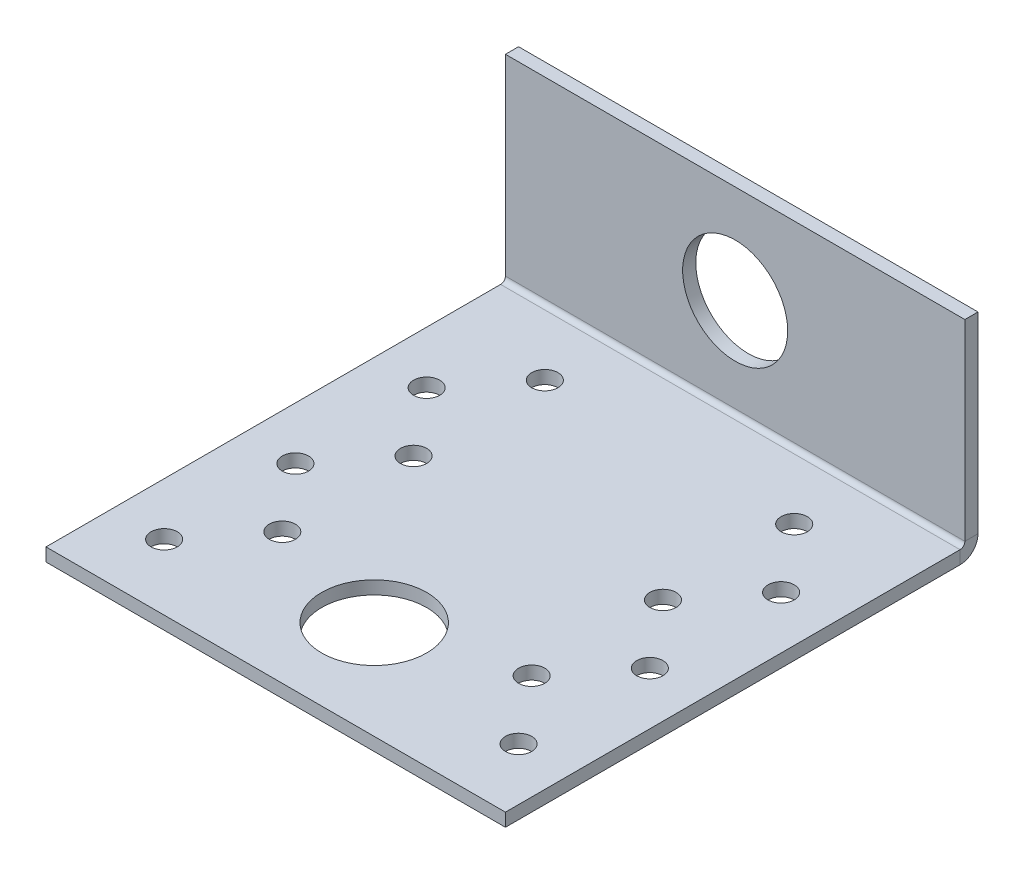
SolidWorks part; units mm, degrees
note: The reader was unsure of these and kept them because the rebuilt part matched: flange length of "Edge-Flange1".
ref_plane "Front Plane" through (0, 0, 0) normal (0, 0, 1) x (1, 0, 0)
ref_plane "Top Plane" through (0, 0, 0) normal (0, 1, 0) x (1, 0, 0)
ref_plane "Right Plane" through (0, 0, 0) normal (1, 0, 0) x (0, 0, -1)
sketch "Sketch1" plane through (0, 0, 0) normal (0, 1, 0) x (1, 0, 0)
  line L1 (-35, 35) -> (35, 35)
  line L2 (-35, 35) -> (-35, -35)
  line L3 (-35, -35) -> (35, -35)
  line L4 (35, 35) -> (35, -35)
  line L5 (-35, 35) -> (35, -35) construction
  line L6 (-35, -35) -> (35, 35) construction
  point P0 (0, 0)
  dimension "D1" = 70
  dimension "D2" = 70
base flange "Base-Flange1" sketch "Sketch1" thickness 2 reverse thickness direction no parameters "D1"=0.7366
edge flange "Edge-Flange1" sketch "Sketch8" flange angle 90 flange length 30 flange position material outside bend radius 0.7366 thickness 2 relief rectangular parameters "D6"=0
sketch "Sketch8" plane through (0, 0, -35) normal (0, 0, -1) x (-1, 0, 0)
  line L0 (-35, 0) -> (35, 0) construction
  line L1 (-35, 0) -> (35, 0)
  line L2 (-35, 0) -> (-35, 30)
  line L3 (-35, 30) -> (35, 30)
  line L4 (35, 30) -> (35, 0)
bend "EdgeBend1" bend radius 0.7366 bend angle 90 parameters "D5"=1
sketch "Sketch9" plane through (0, 0, -35) normal (0, 0, 1) x (1, 0, 0)
  line L0 (-35, 30) -> (35, 30) construction
  line L2 (35, 30) -> (35, 0.7366) construction
  line L3 (0, 0) -> (0, 30) construction
  circle A0 centre (0, 15) radius 8
  dimension "D1" = 16
  dimension "D2" = 15
  dimension "D7" = 35
extrude "Cut-Extrude1" cut sketch "Sketch9" against normal blind 10
sketch "Sketch11" plane through (0, -2, 0) normal (0, -1, 0) x (1, 0, 0)
  line L0 (0, -34.2634) -> (0, 35) construction
  line L1 (-35, -34.2634) -> (35, -34.2634) construction
  line L2 (-35, 35) -> (35, 35) construction
  line L3 (-35, -34.2634) -> (-35, 35) construction
  circle A0 centre (0, 20) radius 8
  circle A1 centre (-27, 25) radius 2
  circle A2 centre (-19, 15) radius 2
  circle A3 centre (-27, 5) radius 2
  circle A4 centre (-19, -5) radius 2
  circle A5 centre (-27, -15) radius 2
  circle A6 centre (-19, -25) radius 2
  circle A7 centre (27, 5) radius 2
  circle A8 centre (19, 15) radius 2
  circle A9 centre (19, -25) radius 2
  circle A10 centre (27, -15) radius 2
  circle A11 centre (19, -5) radius 2
  circle A12 centre (27, 25) radius 2
  dimension "D1" = 15
  dimension "D2" = 10
  dimension "D3" = 8
  dimension "D4" = 8
  dimension "D5" = 4
  dimension "D6" = 10
  dimension "D7" = 10
  dimension "D8" = 10
  dimension "D9" = 10
  dimension "D10" = 10
  dimension "D11" = 16
extrude "Cut-Extrude2" cut sketch "Sketch11" against normal blind 10
sketch "Bend-Lines1" [suppressed] plane through (0, 0, 0) normal (0, 1, 0) x (1, 0, 0)
sketch "Bounding-Box1" [suppressed] plane through (0, 0, 0) normal (0, 1, 0) x (1, 0, 0)
sheet metal parameters "Sheet-Metal1" thickness 2 parameters "D1"=0.7366
flat pattern "Flat-Pattern1" [suppressed]
sketch "Bend-Lines2" plane through (0, 0, 0) normal (0, 1, 0) x (1, 0, 0)
sketch "Bounding-Box2" [suppressed] plane through (0, 0, 0) normal (0, 1, 0) x (1, 0, 0)
sheet metal parameters "Sheet-Metal2" thickness 2 parameters "D1"=0.7366
flat pattern "Flat-Pattern1" [suppressed]
sketch "Bend-Lines2" plane through (0, 0, 0) normal (0, 1, 0) x (1, 0, 0)
sketch "Bounding-Box2" [suppressed] plane through (0, 0, 0) normal (0, 1, 0) x (1, 0, 0)
bend of the flat pattern "Flatten-<EdgeBend1>1"
sheet metal parameters "Sheet-Metal3" thickness 2 parameters "D1"=0.7366
flat pattern "Flat-Pattern1" [suppressed]
sketch "Bend-Lines2" plane through (0, 0, 0) normal (0, 1, 0) x (1, 0, 0)
sketch "Bounding-Box2" [suppressed] plane through (0, 0, 0) normal (0, 1, 0) x (1, 0, 0)
bend of the flat pattern "Flatten-<EdgeBend1>1"
sheet metal parameters "Sheet-Metal4" thickness 2 parameters "D1"=0.7366
flat pattern "Flat-Pattern1"
sketch "Bend-Lines2" plane through (0, 0, 0) normal (0, 1, 0) x (1, 0, 0)
  line L0 (35, 35.6273) -> (-35, 35.6273) construction
  line L1 (35, 35.6273) -> (-35, 35.6273) construction
sketch3d "Bounding-Box2" [suppressed]
  line L0 (-35, 66.2546, 0) -> (-35, -35, 0) construction
  line L1 (35, 66.2546, 0) -> (35, -35, 0) construction
  line L2 (-35, 66.2546, 0) -> (35, 66.2546, 0) construction
  line L3 (-35, -35, 0) -> (35, -35, 0) construction
bend of the flat pattern "Flatten-<EdgeBend1>1"
